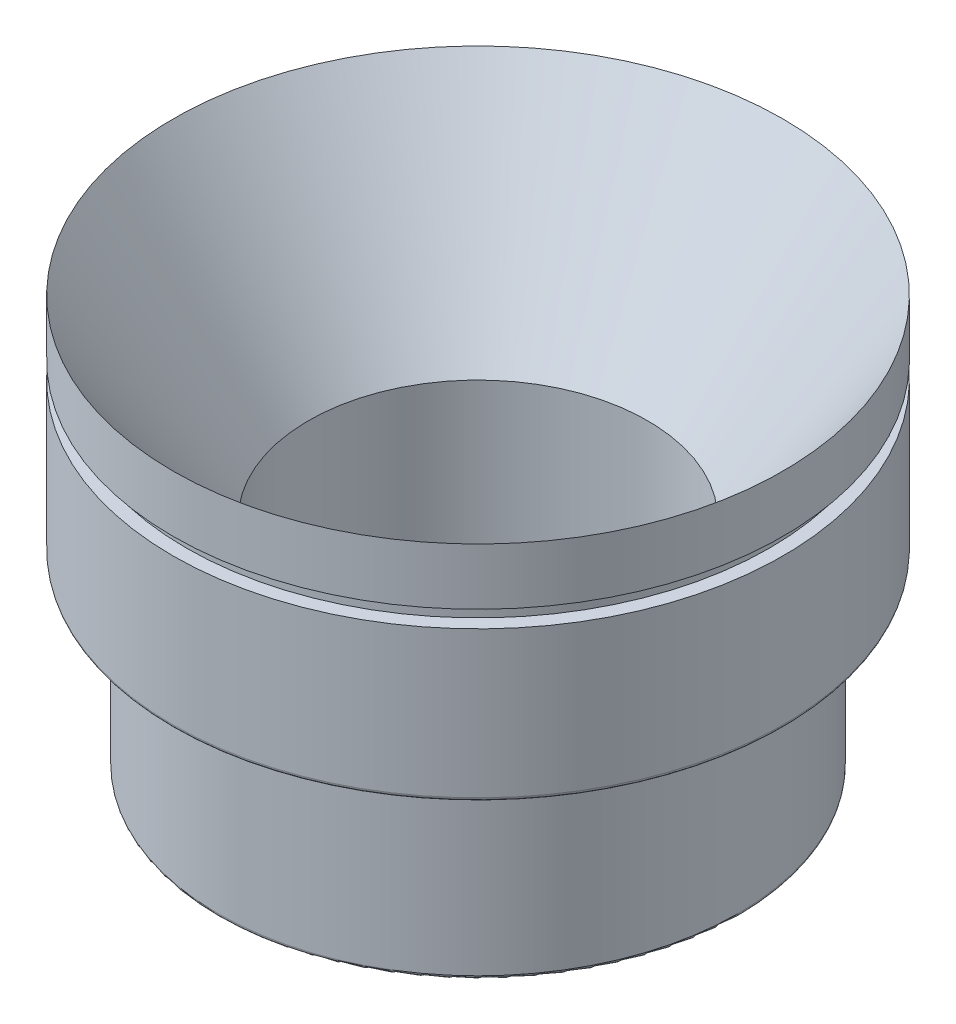
SolidWorks part; units mm, degrees
material "C (Graphite)"
ref_plane "Front Plane" through (0, 0, 0) normal (0, 0, 1) x (1, 0, 0)
ref_plane "Top Plane" through (0, 0, 0) normal (0, 1, 0) x (1, 0, 0)
ref_plane "Right Plane" through (0, 0, 0) normal (1, 0, 0) x (0, 0, -1)
sketch "Sketch4" plane through (0, 0, 0) normal (1, 0, 0) x (0, 0, -1)
  line L0 (0, 0) -> (0, -131.2074) construction
  line L1 (34.2773, 0) -> (23.8732, -14.8586) construction
  line L2 (19.05, -81.8573) -> (19.05, -89.5311) construction
  line L3 (22.2956, -54.8084) -> (51.1382, -162.4506) construction
  line L4 (34.2773, 0) -> (19.05, -21.7468)
  line L17 (34.2773, 0) -> (34.2773, -25.1013)
  line L18 (34.2773, -25.1013) -> (29.1846, -25.1013)
  line L19 (29.1846, -25.1013) -> (29.1846, -46.0309)
  line L20 (29.1846, -46.0309) -> (20.3822, -46.0309)
  line L22 (20.3822, -46.0309) -> (19.05, -38.1493)
  line L24 (19.05, -21.7468) -> (19.05, -38.1493)
  arc A1 (23.8732, -14.8586) -> (19.05, -30.1559) centre (45.72, -30.1559) ccw construction
  arc A2 (19.05, -30.1559) -> (22.2956, -54.8084) centre (114.3, -30.1559) ccw construction
  dimension "D4" = 26.67
  dimension "D6" = 95.25
  dimension "D3" = 35
  dimension "D5" = 38.1
  dimension "D7" = 15
  dimension "D15" = 3.2456
  dimension "D19" = 10.1346
  dimension "D20" = 5.0546
  dimension "D21" = 15.875
  dimension "D11" = 68.5546
  dimension "D24" = 58.3692
revolve "Revolve1" add sketch "Sketch4" angle 360 about L0
sketch "Sketch6" plane through (0, 0, 0) normal (1, 0, 0) x (0, 0, -1)
  line L0 (34.2773, -6.35) -> (32.766, -6.35)
  line L1 (32.766, -6.35) -> (32.766, -8.255)
  line L2 (32.766, -8.255) -> (34.2773, -8.255)
  line L3 (34.2773, -8.255) -> (34.2773, -6.35)
  line L4 (-34.2773, 0) -> (34.2773, 0) construction
  line L5 (-34.2773, 0) -> (34.2773, 0) construction
  line L6 (0, 11.3644) -> (0, 4.9299) construction
  dimension "D1" = 65.532
  dimension "D2" = 1.905
  dimension "D3" = 6.35
revolve "Spring Groove" cut sketch "Sketch6" angle 360 about L6
fillet "Tool Radius" radius 0.4064 2 edges at (0, -46.0309, 29.1846) (0, -25.1013, 34.2773)
equation "\"Dc\"= 114.30mm"
equation "\"Dt\"= 38.1mm"
equation "\"R1\"= 26.67mm"
equation "\"R2\"= 92mm"
equation "\"b\"= 35deg"
equation "\"Rn\"= 95.25mm"
equation "\"Tn\"= 15deg"
equation "\"Te\"= 3deg"
equation "\"De\"= 87.31mm"
equation "\"Le\"= 146.71mm"
equation "\"D5@Sketch4\"=\"Dt\""
equation "\"WallThickness\"=0.5"
equation "\"Rt\"=1.5"
